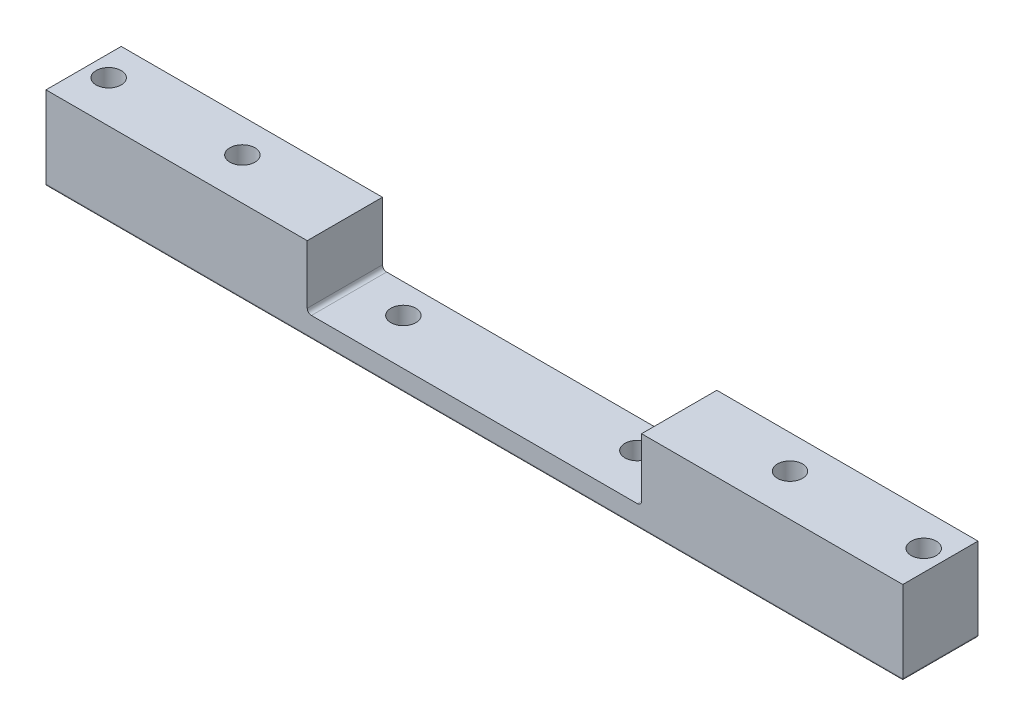
SolidWorks part; units mm, degrees
ref_plane "Front Plane" through (0, 0, 0) normal (0, 0, 1) x (1, 0, 0)
ref_plane "Top Plane" through (0, 0, 0) normal (0, 1, 0) x (1, 0, 0)
ref_plane "Right Plane" through (0, 0, 0) normal (1, 0, 0) x (0, 0, -1)
sketch "Sketch1" plane through (0, 0, 0) normal (0, 1, 0) x (1, 0, 0)
  line L0 (142.5033, 0) -> (142.5033, -18)
  line L1 (0, 0) -> (205, 0)
  line L2 (0, 0) -> (0, -18)
  line L3 (0, -18) -> (205, -18)
  line L4 (205, 0) -> (205, -18)
  line L5 (62.5033, 0) -> (62.5033, -18)
  circle A0 centre (4.99, -8) radius 3
  circle A1 centre (36.99, -8) radius 3
  circle A2 centre (74.5033, -7) radius 3
  circle A3 centre (130.5033, -7) radius 3
  circle A4 centre (168.0133, -8) radius 3
  circle A5 centre (200.0133, -8) radius 3
  dimension "D5" = 6
  dimension "D6" = 6
  dimension "D1" = 205
  dimension "D2" = 18
  dimension "D3" = 8
  dimension "D4" = 7
  dimension "D7" = 32
  dimension "D8" = 56
  dimension "D9" = 32
  dimension "D10" = 37.5133
  dimension "D11" = 37.51
  dimension "D12" = 4.99
  dimension "D13" = 4.9867
  dimension "D14" = 80
  dimension "D15" = 12
extrude "Boss-Extrude1" add sketch "Sketch1" along normal blind 20 contours L5 L1 L2 L3 A1 A0 | L4 L1 L0 L3 A5 A4 region at (173.2085, 0, 9.0529) region at (31.7947, 0, 9.0529)
extrude "Boss-Extrude2" add sketch "Sketch1<3>" along normal blind 5 contours L1 L5 L3 L0 A3 A2 region at (102.5033, 0, 9.0818)
sketch "Sketch1<3>" plane through (0, 0, 0) normal (0, 1, 0) x (1, 0, 0) same geometry as "Sketch1"
fillet "Fillet1" radius 0.5 10 edges at (168.0133, 0, 11) (200.0133, 0, 11) (74.5033, 0, 10) (130.5033, 0, 10) (0, 0, 9) (102.5, 0, 18) (205, 0, 9) (102.5, 0, 0) (4.99, 0, 11) (36.99, 0, 11)
fillet "Fillet2" radius 1 2 edges at (62.5033, 5, 9) (142.5033, 5, 9)
